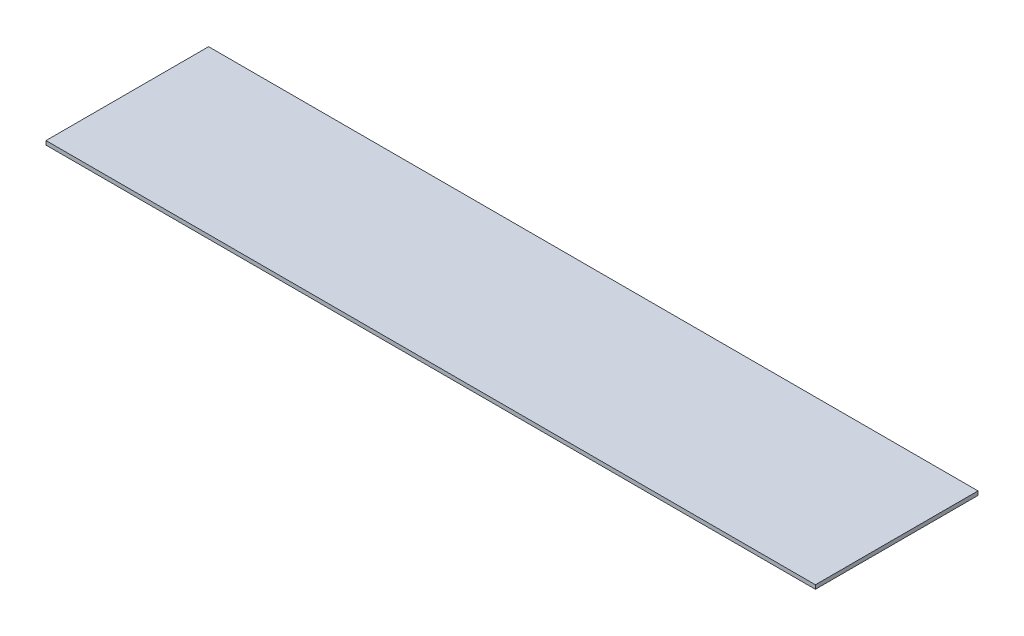
SolidWorks part; units mm, degrees
ref_plane "Front Plane" through (0, 0, 0) normal (0, 0, 1) x (1, 0, 0)
ref_plane "Top Plane" through (0, 0, 0) normal (0, 1, 0) x (1, 0, 0)
ref_plane "Right Plane" through (0, 0, 0) normal (1, 0, 0) x (0, 0, -1)
sketch "Sketch1" plane through (0, 0, 0) normal (0, 1, 0) x (1, 0, 0)
  line L1 (-307.975, -65.0875) -> (307.975, -65.0875)
  line L2 (-307.975, -65.0875) -> (-307.975, 65.0875)
  line L3 (-307.975, 65.0875) -> (307.975, 65.0875)
  line L4 (307.975, -65.0875) -> (307.975, 65.0875)
  line L5 (-307.975, -65.0875) -> (307.975, 65.0875) construction
  line L6 (-307.975, 65.0875) -> (307.975, -65.0875) construction
  point P0 (0, 0)
  point P6 (0, 0)
  dimension "D1" = 130.175
  dimension "D2" = 615.95
extrude "Boss-Extrude1" add sketch "Sketch1" along normal blind 3.175
